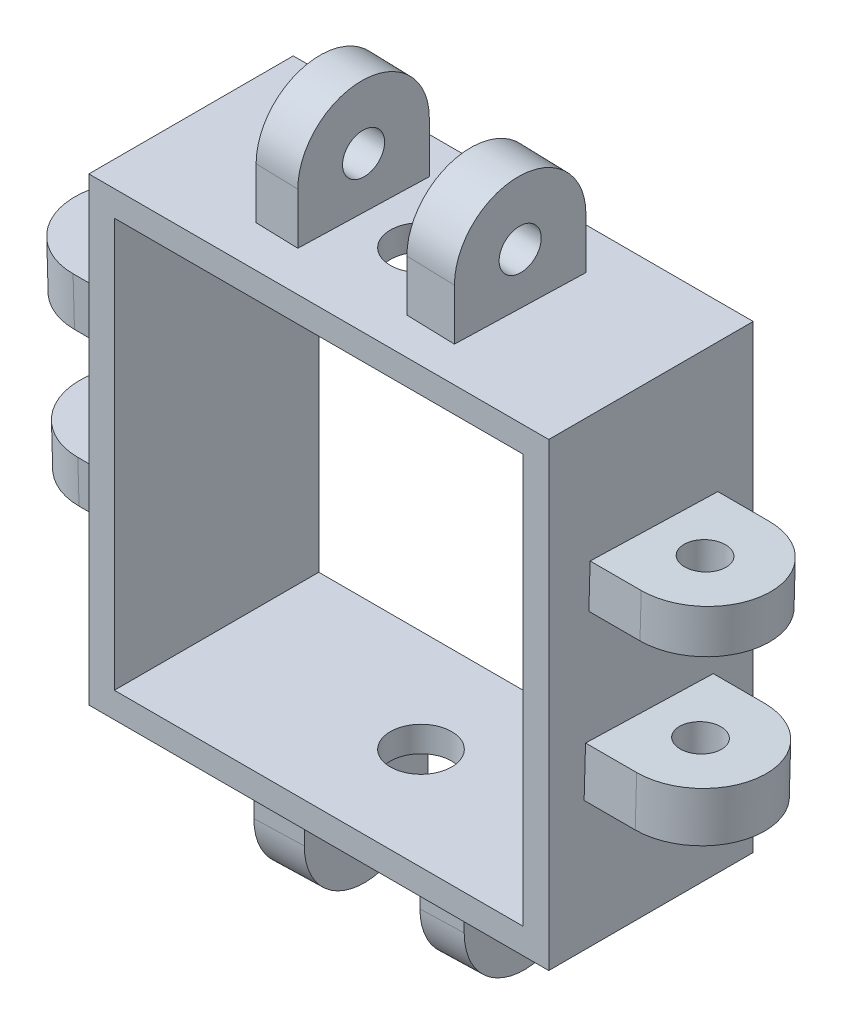
SolidWorks part; units mm, degrees
material "2024 合金"
ref_plane "前视基准面" through (0, 0, 0) normal (0, 0, 1) x (1, 0, 0)
ref_plane "上视基准面" through (0, 0, 0) normal (0, 1, 0) x (1, 0, 0)
ref_plane "右视基准面" through (0, 0, 0) normal (1, 0, 0) x (0, 0, -1)
sketch "草图1" plane through (0, 0, 0) normal (0, 0, 1) x (1, 0, 0)
  line L1 (-45, -45) -> (45, -45)
  line L2 (-45, -45) -> (-45, 45)
  line L3 (-45, 45) -> (45, 45)
  line L4 (45, -45) -> (45, 45)
  line L5 (-45, -45) -> (45, 45) construction
  line L6 (-45, 45) -> (45, -45) construction
  line L7 (-40, -40) -> (40, -40)
  line L8 (-40, -40) -> (-40, 40)
  line L9 (-40, 40) -> (40, 40)
  line L10 (40, -40) -> (40, 40)
  line L11 (-40, -40) -> (40, 40) construction
  line L12 (-40, 40) -> (40, -40) construction
  point P0 (0, 0)
  point P7 (0, 0)
  dimension "D1" = 90
  dimension "D2" = 90
  dimension "D3" = 80
  dimension "D4" = 80
extrude "凸台-拉伸1" add sketch "草图1" along normal blind 40
sketch "草图3" plane through (0, 45, 0) normal (0, 1, 0) x (1, 0, 0)
  line L0 (0, 0) -> (0, -20) construction
  line L1 (45, 0) -> (-45, 0) construction
  circle A0 centre (0, -20) radius 6
  dimension "D2" = 12
  dimension "D1" = 20
extrude "切除-拉伸2" cut sketch "草图3" against normal through all
sketch "草图4" plane through (1.5966, -1.9977, 74.2418) normal (0.9996, 0, -0.0294) x (-0.0294, 0, -0.9996)
  line L0 (41.7652, -43.0023) -> (41.7652, -53.0023)
  line L1 (66.7652, -53.0023) -> (66.7652, -43.0023)
  line L2 (66.7652, -43.0023) -> (41.7652, -43.0023)
  line L3 (54.2652, -42.5) -> (54.2652, -53.0023) construction
  line L4 (35.5979, -43.0023) -> (75.5806, -43.0023) construction
  arc A0 (41.7652, -53.0023) -> (66.7652, -53.0023) centre (54.2652, -53.0023) ccw
  circle A1 centre (54.2652, -53.0023) radius 4
  dimension "D3" = 8
  dimension "D1" = 25
  dimension "D2" = 10
extrude "凸台-拉伸2" add sketch "草图4" along normal blind 20 and the other way blind 20
sketch "草图5" plane through (0.2204, 0, 7.4881) normal (-0.0294, 0, -0.9996) x (-0.9996, 0, 0.0294)
  line L0 (0, 0) -> (0, -60) construction
  line L1 (11, -45) -> (-11, -45)
  line L2 (11, -45) -> (11, -75)
  line L3 (11, -75) -> (-11, -75)
  line L4 (-11, -45) -> (-11, -75)
  line L5 (11, -45) -> (-11, -75) construction
  line L6 (11, -75) -> (-11, -45) construction
  line L7 (44.9805, -45) -> (-44.9805, -45) construction
  point P0 (0, -60)
  dimension "D1" = 22
  dimension "D2" = 30
extrude "切除-拉伸3" cut sketch "草图5" against normal through all
ref_plane "基准面1" through (0, 0, 0) normal (0, -1, 0) x (-1, 0, 0)
ref_plane "基准面2" through (0, 0, 0) normal (1, 0, 0) x (0, 0, -1)
ref_axis "基准轴1" through (0, 0, 42) along (0, 0, -1)
pattern_circular "阵列(圆周)3" count 4 over 360 about axis through (0, 0, 42) along (0, 0, -1) of "切除-拉伸3", "凸台-拉伸2"
